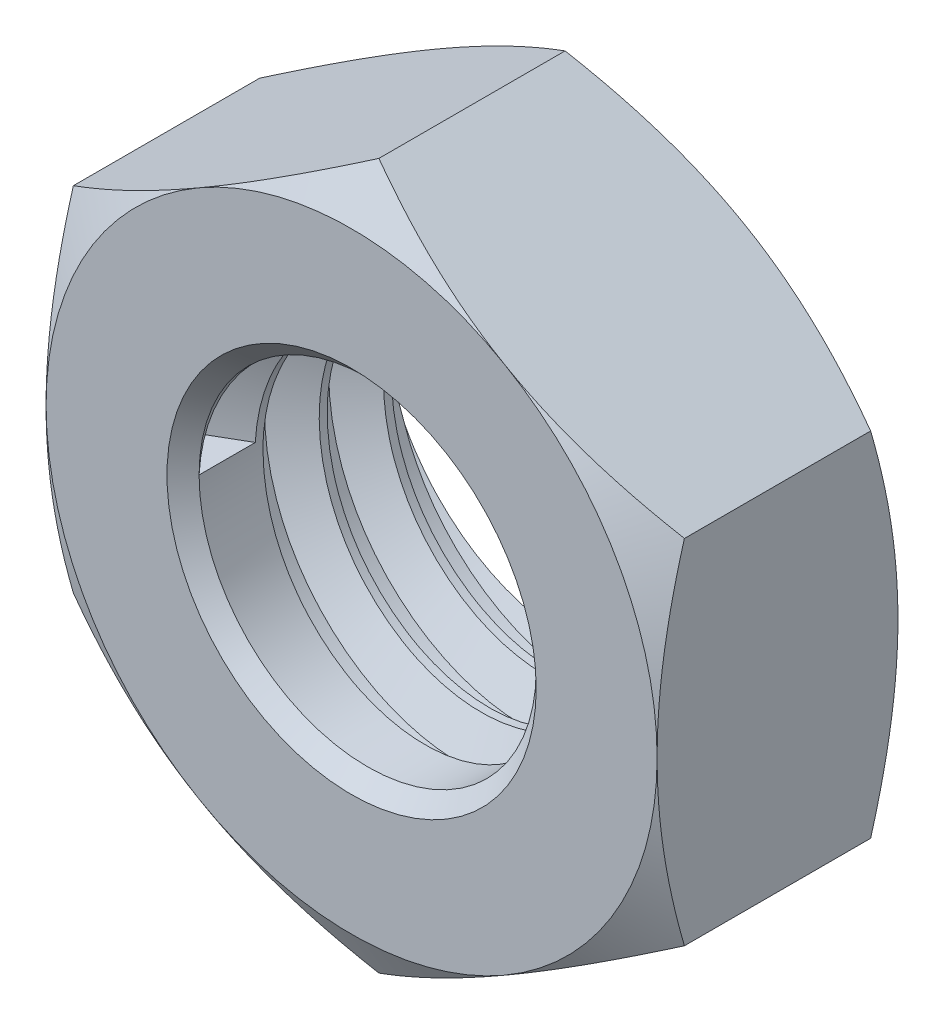
SolidWorks part; units mm, degrees
material "2024 Alloy (SN)"
ref_plane "Front Plane" through (0, 0, 0) normal (0, 0, 1) x (1, 0, 0)
ref_plane "Top Plane" through (0, 0, 0) normal (0, 1, 0) x (1, 0, 0)
ref_plane "Right Plane" through (0, 0, 0) normal (1, 0, 0) x (0, 0, -1)
sketch "Sketch1" plane through (0, 0, 0) normal (0, 0, 1) x (1, 0, 0)
  line L1 (3.8062, -2.1975) -> (3.8062, 2.1975)
  line L2 (3.8062, 2.1975) -> (0, 4.395)
  line L3 (0, 4.395) -> (-3.8062, 2.1975)
  line L4 (-3.8062, 2.1975) -> (-3.8062, -2.1975)
  line L5 (-3.8062, -2.1975) -> (0, -4.395)
  line L6 (0, -4.395) -> (3.8062, -2.1975)
  circle A0 centre (0, 0) radius 3.8062 construction
  dimension "D1" = 8.79
extrude "Boss-Extrude1" add sketch "Sketch1" along normal blind 3
sketch "Sketch2" plane through (0, 0, 0) normal (0, 0, -1) x (-1, 0, 0)
  circle A0 centre (0, 0) radius 3.8062
extrude "Cut-Extrude1" cut sketch "Sketch2" against normal blind 3 draft 60 flip side to cut
ref_plane "Plane1" through (0, 0, 1.5) normal (0, 0, -1) x (-1, 0, 0)
mirror "Mirror1" about plane through (0, 0, 1.5) normal (0, 0, -1) of "Cut-Extrude1"
hole_wizard "M5x0.8 Tapped Hole1" positions "Sketch3" profile "Sketch4" tap size "M5x0.8" standard "ANSI Metric" end condition through all
sketch "Sketch3" plane through (0, 0, 0) normal (0, 0, -1) x (-1, 0, 0)
  point P0 (0, 0)
sketch "Sketch4" plane through (0, 0, 0) normal (1, 0, 0) x (0, 1, 0)
  line L0 (0, 0) -> (0, 3)
  line L1 (0, 3) -> (2.1, 3)
  line L2 (2.1, 3) -> (2.1, 0)
  line L5 (2.1, 0) -> (0, 0)
  line L11 (0, -6.35) -> (0, 107.95) construction
  dimension "Thru Tap Drill Dia." = 4.2
  dimension "Thru Tap Drill Depth" = 3
cosmetic thread "Hole Thread1" parameters "D2"=5
chamfer "Chamfer1" distance 0.2 angle 45 2 edges at (-2.1, 0, 3) (-2.1, 0, 0)
ref_plane "Plane3" through (0, 0, 0.2) normal (0, 0, 1) x (1, 0, 0)
thread "Thread1" pitch 0.8 method cut profile "Thread Profile2" start angle 0, offset 0, length 0, pitch 0.8, diameter 4.2
ref_plane "Plane4" through (-2.1, 0, 2.8) normal (0, -1, 0) x (-1, 0, 0)
sketch "Thread Profile2" plane through (-2.1, 0, 2.8) normal (0, -1, 0) x (-1, 0, 0)
  line L0 (0, 0) -> (0, 0.8) construction
  line L11 (0, 0.7) -> (0, 0)
  line L12 (0, 0) -> (0.433, 0.25)
  line L13 (0.433, 0.25) -> (0.433, 0.45)
  line L15 (0.433, 0.45) -> (0, 0.7)
  line L17 (0.433, 0.35) -> (0, 0.35) construction
  point P3 (0, 0)
  dimension "Pitch" = 0.8
  dimension "Profile_Angle" = 60
  dimension "Profile_Land" = 0.2
  dimension "Profile_Height" = 0.433
